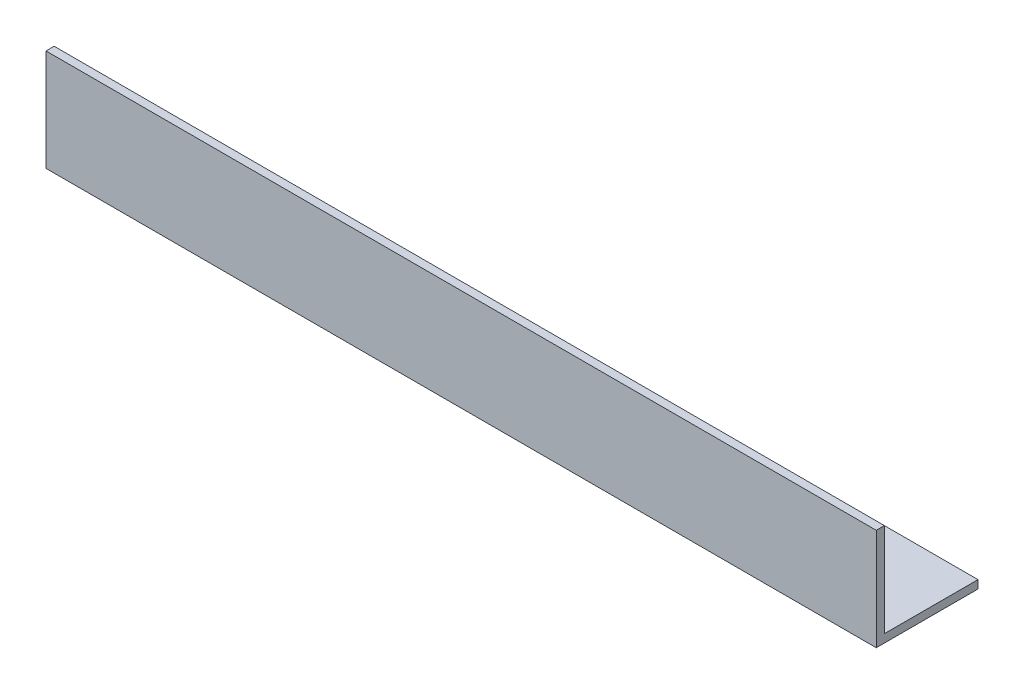
SolidWorks part; units mm, degrees
ref_plane "Спереди" through (0, 0, 0) normal (0, 0, 1) x (1, 0, 0)
ref_plane "Сверху" through (0, 0, 0) normal (0, 1, 0) x (1, 0, 0)
ref_plane "Справа" through (0, 0, 0) normal (1, 0, 0) x (0, 0, -1)
sketch "Эскиз1" plane through (0, 0, 0) normal (1, 0, 0) x (0, 0, -1)
  line L0 (0, 25) -> (0, 0)
  line L1 (0, 0) -> (25, 0)
extrude "Вытянуть-Тонкостенный1" add sketch "Эскиз1" along normal blind 204 thin thin type one direction reverse wall 2
